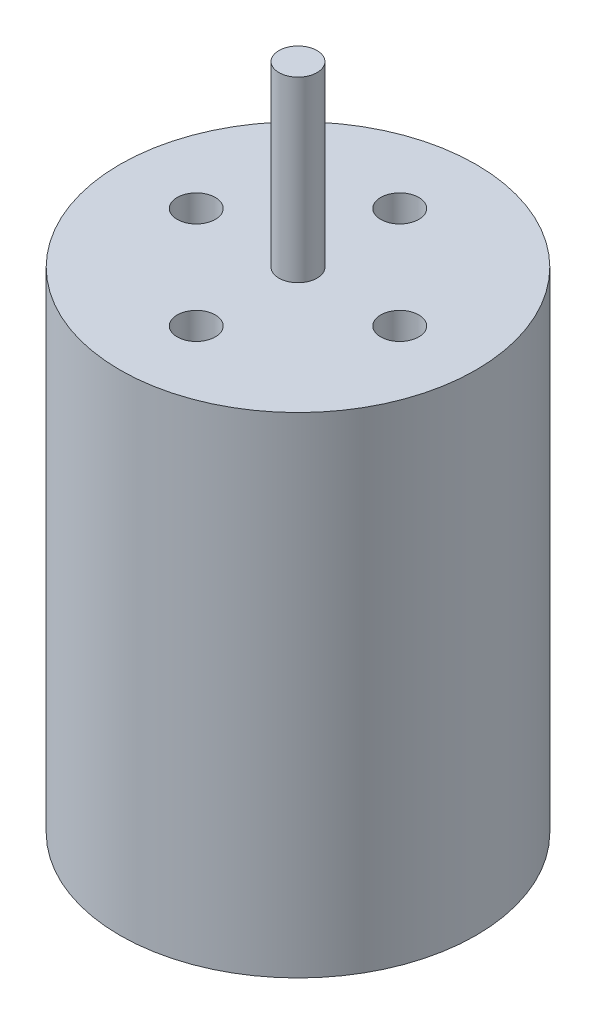
SolidWorks part; units mm, degrees
ref_plane "Front Plane" through (0, 0, 0) normal (0, 0, 1) x (1, 0, 0)
ref_plane "Top Plane" through (0, 0, 0) normal (0, 1, 0) x (1, 0, 0)
ref_plane "Right Plane" through (0, 0, 0) normal (1, 0, 0) x (0, 0, -1)
sketch "Sketch1" plane through (0, 0, 0) normal (0, 0, 1) x (1, 0, 0)
  line L0 (0, -23.4674) -> (0, 16.5224) construction
  line L1 (0, -27.5) -> (4.4, -27.5)
  line L2 (4.4, -27.5) -> (4.4, -25)
  line L3 (4.4, -25) -> (14, -25)
  line L4 (14, -25) -> (14, 13.5)
  line L5 (14, 13.5) -> (1.5, 13.5)
  line L6 (1.5, 13.5) -> (1.5, 27.5)
  line L7 (1.5, 27.5) -> (0, 27.5)
  line L8 (0, 27.5) -> (0, -27.5)
  dimension "D1" = 55
  dimension "D2" = 3
  dimension "D3" = 28
  dimension "D4" = 8.8
  dimension "D5" = 38.5
  dimension "D6" = 14
revolve "Revolve1" add sketch "Sketch1" angle 360 about L0
sketch "Sketch2" plane through (0, 13.5, 0) normal (0, 1, 0) x (1, 0, 0)
  line L0 (-8, 0) -> (0, -8) construction
  line L1 (-8, 0) -> (0, 8) construction
  line L2 (0, -8) -> (8, 0) construction
  line L3 (0, 8) -> (8, 0) construction
  line L4 (-8, 0) -> (8, 0) construction
  line L5 (0, -8) -> (0, 8) construction
  circle A0 centre (-8, 0) radius 1.5
  circle A1 centre (0, -8) radius 1.5
  circle A2 centre (8, 0) radius 1.5
  circle A3 centre (0, 8) radius 1.5
  point P1 (0, 0)
  dimension "D1" = 3
  dimension "D2" = 16
extrude "Cut-Extrude1" cut sketch "Sketch2" against normal blind 3
